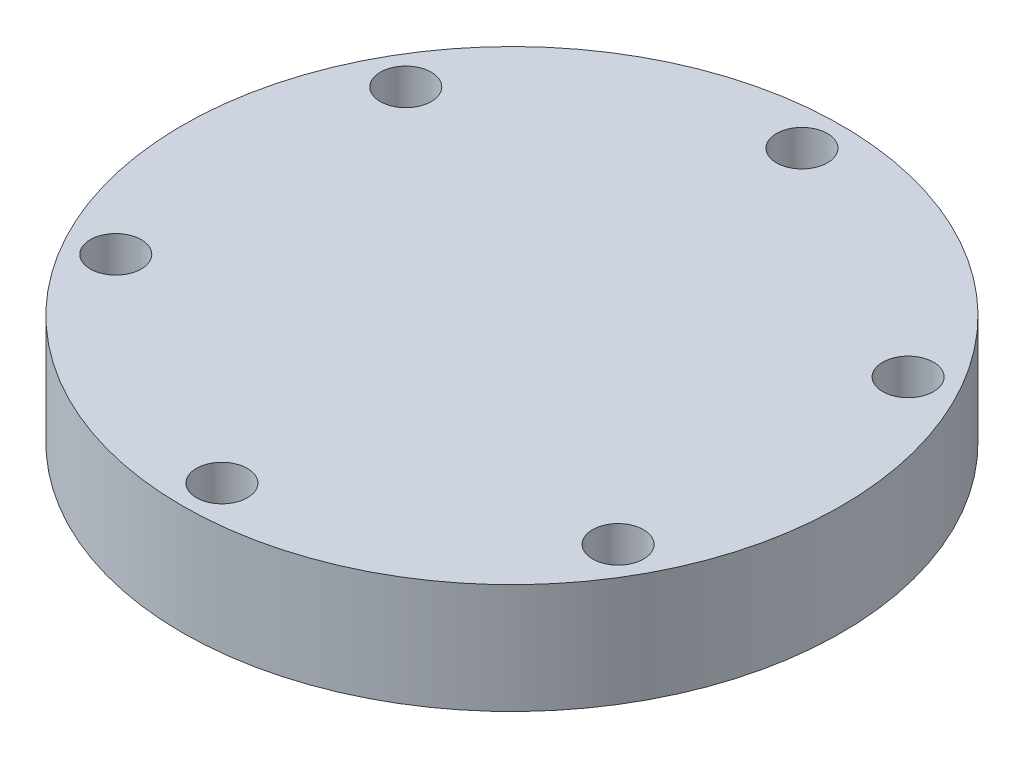
SolidWorks part; units mm, degrees
material "Copper"
ref_plane "Front Plane" through (0, 0, 0) normal (0, 0, 1) x (1, 0, 0)
ref_plane "Top Plane" through (0, 0, 0) normal (0, 1, 0) x (1, 0, 0)
ref_plane "Right Plane" through (0, 0, 0) normal (1, 0, 0) x (0, 0, -1)
ref_axis "Y Axis" through (0, 6.6675, 0) along (0, -1, 0)
sketch "outer" plane through (0, 0, 0) normal (0, 1, 0) x (1, 0, 0)
  circle A0 centre (0, 0) radius 19.05
  dimension "D1" = 38.1
extrude "Body" add sketch "outer" along normal blind 6.35
sketch "inner" plane through (0, 0, 0) normal (0, 1, 0) x (1, 0, 0)
  circle A0 centre (0, 0) radius 11.938
  dimension "D1" = 23.876
extrude "Pocket" cut sketch "inner" along normal blind 3.81
sketch "Screw Position" plane through (0, 0, 0) normal (0, 1, 0) x (1, 0, 0)
  point P0 (0, 16.764)
  dimension "D1" = 16.764
hole_wizard "#4 Clearance Hole1" positions "Sketch7" profile "Sketch8" hole size "#4" standard "ANSI Inch" end condition through all
sketch "Sketch7" plane through (0, 6.35, 0) normal (0, 1, 0) x (1, 0, 0)
  point P0 (0, 16.764)
sketch "Sketch8" plane through (0, 6.35, -16.764) normal (1, 0, 0) x (0, 0, 1)
  line L0 (0, 0) -> (0, 6.35)
  line L1 (0, 6.35) -> (1.4732, 6.35)
  line L2 (1.4732, 6.35) -> (1.4732, 0)
  line L5 (1.4732, 0) -> (0, 0)
  line L11 (0, -6.35) -> (0, 107.95) construction
  dimension "Thru Hole Dia." = 2.9464
  dimension "Thru Hole Depth" = 6.35
pattern_circular "Screw Holes" count 6 over 360 about axis through (0, 6.6675, 0) along (0, -1, 0) of "#4 Clearance Hole1"
sketch "Post Sketch" plane through (0, 0, 0) normal (0, 1, 0) x (1, 0, 0)
  circle A1 centre (5.3033, -5.3033) radius 1.2065
  point P0 (0, -7)
  point P1 (5.3033, -5.3033)
  dimension "D4" = 2.413
  dimension "D1" = 7
  dimension "D2" = 7.5
extrude "Post" add sketch "Post Sketch" against normal blind 4.572 from surface starting at face at (0, 3.81, 11.938)
pattern_circular "Posts" count 4 over 360 about axis through (0, 6.6675, 0) along (0, -1, 0) of "Post"
equation "\"outer_d\"= 3 / 2in"
equation "\"top_h\"= 1 / 4in"
equation "\"screw_r\"= 0.66in"
equation "\"inner_d\"= 0.94in"
equation "\"inner_h\"= 150mil"
equation "\"D1@outer\" = \"outer_d\""
equation "\"D1@Body\" = \"top_h\""
equation "\"D1@inner\"=\"inner_d\""
equation "\"D1@Pocket\" = \"inner_h\""
equation "\"D1@Screw Position\"=\"screw_r\""
equation "\"post_r1\"= 7mm"
equation "\"post_r2\"= 7.5mm"
equation "\"post_bottom_h\"= 0.03in"
equation "\"D1@Post Sketch\" = \"post_r1\""
equation "\"D2@Post Sketch\" = \"post_r2\""
equation "\"post_d\"= 0.095in"
equation "\"D4@Post Sketch\"=\"post_d\""
equation "\"D1@Post\" = \"inner_h\" + \"post_bottom_h\""
